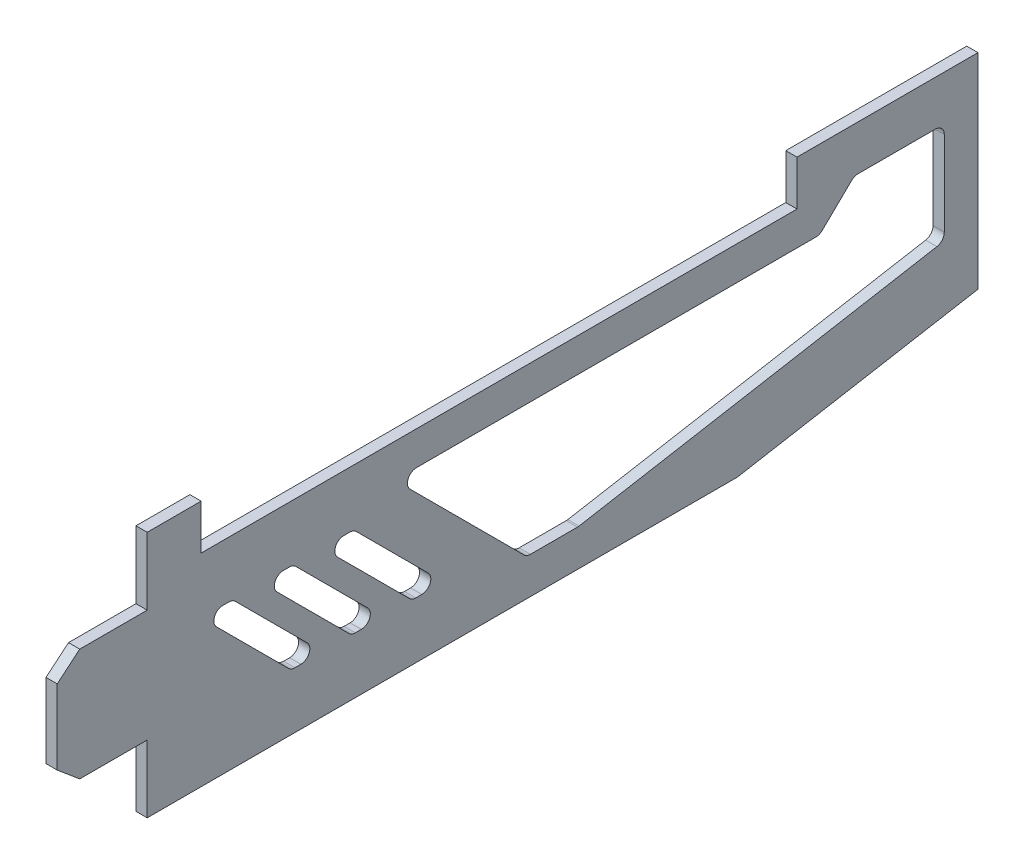
SolidWorks part; units mm, degrees
ref_plane "Ebene vorne" through (0, 0, 0) normal (0, 0, 1) x (1, 0, 0)
ref_plane "Ebene oben" through (0, 0, 0) normal (0, 1, 0) x (1, 0, 0)
ref_plane "Ebene rechts" through (0, 0, 0) normal (1, 0, 0) x (0, 0, -1)
sketch "Skizze1" plane through (0, 0, 0) normal (1, 0, 0) x (0, 0, -1)
  line L1 (0, 0) -> (369.5, 0)
  line L2 (0, 0) -> (0, 110)
  line L3 (0, 110) -> (369.5, 110)
  line L4 (369.5, 0) -> (369.5, 110)
  dimension "D1" = 110
  dimension "D2" = 369.5
extrude "Grundplatte" add sketch "Skizze1" along normal blind 5
sketch "Skizze2" plane through (5, 0, 0) normal (1, 0, 0) x (0, 0, -1)
  line L0 (262.5, 0) -> (369.5, 18.867)
  line L1 (0, 0) -> (369.5, 0) construction
  line L2 (369.5, 0) -> (369.5, 110) construction
  line L3 (369.5, 18.867) -> (369.5, 0)
  line L4 (369.5, 0) -> (262.5, 0)
  dimension "D1" = 170
  dimension "D2" = 262.5
extrude "HeckSchräge" cut sketch "Skizze2" against normal through all
sketch "Skizze3" plane through (5, 0, 0) normal (1, 0, 0) x (0, 0, -1)
  line L0 (369.5, 110) -> (0, 110) construction
  line L1 (24, 110) -> (289, 110)
  line L2 (24, 110) -> (24, 90)
  line L3 (24, 90) -> (289, 90)
  line L4 (289, 110) -> (289, 90)
  line L5 (0, 110) -> (0, 0) construction
  dimension "D1" = 265
  dimension "D2" = 20
  dimension "D3" = 24
extrude "AusschnittFlächendoppler" cut sketch "Skizze3" against normal blind 5
sketch "Skizze4" plane through (5, 0, 0) normal (1, 0, 0) x (0, 0, -1)
  line L0 (24, 90) -> (24, 45) construction
  line L1 (24, 45) -> (24, 0) construction
  line L2 (0, 0) -> (262.5, 0) construction
  line L3 (24, 45) -> (369.5, 45) construction
  line L4 (369.5, 18.867) -> (369.5, 110) construction
  line L5 (24, 65) -> (64, 25)
  line L6 (24, 65) -> (38, 65)
  line L7 (64, 25) -> (78, 25)
  line L8 (38, 65) -> (78, 25)
  line L9 (24, 90) -> (289, 90) construction
  line L10 (50.8952, 45) -> (396.3952, 45) construction
  line L11 (50.8952, 65) -> (64.8952, 65)
  line L12 (64.8952, 65) -> (104.8952, 25)
  line L13 (90.8952, 25) -> (104.8952, 25)
  line L14 (50.8952, 65) -> (90.8952, 25)
  line L15 (77.7903, 45) -> (423.2903, 45) construction
  line L16 (77.7903, 65) -> (91.7903, 65)
  line L17 (91.7903, 65) -> (131.7903, 25)
  line L18 (117.7903, 25) -> (131.7903, 25)
  line L19 (77.7903, 65) -> (117.7903, 25)
  line L20 (104.6855, 45) -> (450.1855, 45) construction
  line L25 (354.5, 90) -> (354.5, 45)
  line L27 (168.7747, 16.2999) -> (110.0746, 75)
  line L28 (110.0746, 75) -> (299, 75)
  line L29 (299, 75) -> (314.5, 90)
  line L30 (314.5, 90) -> (354.5, 90)
  line L31 (168.7747, 16.2999) -> (191.7339, 16.2999)
  line L33 (369.5, 110) -> (289, 110) construction
  line L34 (289, 90) -> (289, 110) construction
  line L35 (191.7339, 16.2999) -> (354.5, 45)
  line L36 (369.5, 18.867) -> (262.5, 0) construction
  line L37 (144.6855, 25) -> (158.6855, 25) [skipped]
  line L38 (104.6855, 65) -> (144.6855, 25) [skipped]
  line L39 (118.6855, 65) -> (158.6855, 25) [skipped]
  line L40 (104.6855, 65) -> (118.6855, 65) [skipped]
  point P3 (44, 45)
  dimension "D1" = 25
  dimension "D2" = 45
  dimension "D3" = 14
  dimension "D5" = 15
  dimension "D6" = 20
  dimension "D7" = 15
  dimension "D8" = 20
  dimension "D9" = 40
  dimension "D10" = 10
  dimension "D11" = 28.3407
  dimension "D4" = 4
extrude "Schnitt-Linear austragen3" cut sketch "Skizze4" against normal through all
fillet "Verrundung1" radius 4 19 edges at (2.5, 65, -77.7903) (2.5, 65, -91.7903) (2.5, 25, -131.7903) (2.5, 25, -117.7903) (2.5, 25, -90.8952) (2.5, 25, -104.8952) (2.5, 65, -64.8952) (2.5, 65, -50.8952) (2.5, 25, -64) (2.5, 25, -78) (2.5, 65, -38) (2.5, 65, -24) (2.5, 90, -354.5) (2.5, 75, -299) (2.5, 90, -314.5) (2.5, 75, -110.0746) (2.5, 45, -354.5) (2.5, 16.2999, -191.7339) (2.5, 16.2999, -168.7747)
sketch "Skizze5" plane through (5, 0, 0) normal (1, 0, 0) x (0, 0, -1)
  line L0 (0, 80) -> (-30, 80)
  line L1 (0, 110) -> (0, 0) construction
  line L2 (-30, 80) -> (-40, 71.609)
  line L3 (-40, 71.609) -> (-40, 38.391)
  line L4 (-40, 55) -> (0, 55) construction
  line L5 (0, 80) -> (0, 30)
  line L6 (-30, 30) -> (-40, 38.391)
  line L7 (0, 30) -> (-30, 30)
  dimension "D1" = 40
  dimension "D2" = 50
  dimension "D3" = 140
  dimension "D4" = 30
extrude "LascheNase" add sketch "Skizze5" against normal up to surface (5 mm away) up to face at (0, 57.8038, -256.7839)
